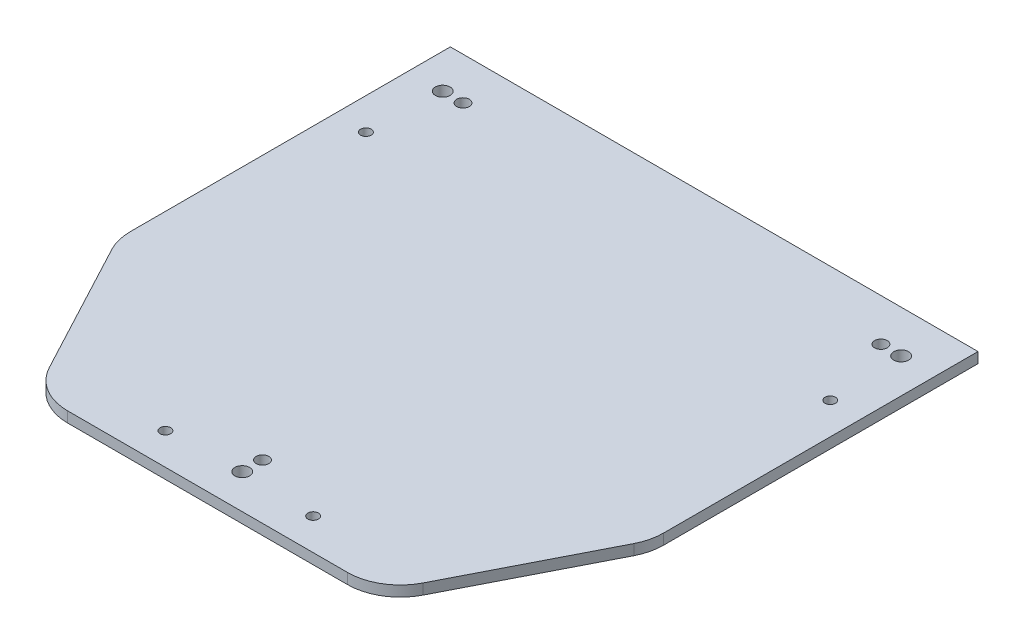
SolidWorks part; units mm, degrees
ref_plane "Plano frontal" through (0, 0, 0) normal (0, 0, 1) x (1, 0, 0)
ref_plane "Plano superior" through (0, 0, 0) normal (0, 1, 0) x (1, 0, 0)
ref_plane "Plano direito" through (0, 0, 0) normal (1, 0, 0) x (0, 0, -1)
sketch "Esboço1" plane through (0, 0, 0) normal (0, 1, 0) x (1, 0, 0)
  line L0 (602.5273, -115.797) -> (470.0074, -115.797)
  line L2 (411.2674, 124.203) -> (661.2674, 124.203)
  line L3 (661.2674, 84.203) -> (661.2674, -24.7556)
  line L4 (411.2674, 81.5882) -> (411.2674, -27.3704)
  line L5 (661.2674, 124.203) -> (661.2674, 84.203)
  line L12 (624.7901, -102.1709) -> (658.5302, -36.1295)
  line L14 (411.2674, 124.203) -> (411.2674, 81.5882)
  line L16 (447.936, -102.538) -> (414.1959, -39.1114)
  arc A0 (414.1959, -39.1114) -> (411.2674, -27.3704) centre (436.2674, -27.3704) cw
  arc A1 (447.936, -102.538) -> (470.0074, -115.797) centre (470.0074, -90.797) ccw
  arc A2 (624.7901, -102.1709) -> (602.5273, -115.797) centre (602.5273, -90.797) cw
  arc A3 (658.5302, -36.1295) -> (661.2674, -24.7556) centre (636.2674, -24.7556) ccw
  dimension "D3" = 240
  dimension "D1" = 25
  dimension "D2" = 250
extrude "Ressalto-extrusão4" add sketch "Esboço1" along normal blind 5 contours L14 region at (536.1641, 0, -10.3309)
sketch "Esboço2" plane through (0, 5, 0) normal (0, 1, 0) x (1, 0, 0)
  line L0 (411.2674, 124.203) -> (661.2674, 124.203) construction
  line L1 (536.2674, -115.797) -> (536.2674, -99.397) construction
  line L2 (426.2674, 69.0882) -> (426.2674, 69.203) construction
  line L3 (426.2674, 69.203) -> (411.2674, 69.203) construction
  line L4 (602.5273, -115.797) -> (470.0074, -115.797) construction
  line L5 (536.2674, -115.797) -> (536.2674, -89.797) construction
  line L6 (571.2674, -115.797) -> (571.2674, -100.797) construction
  line L7 (571.2674, -100.797) -> (568.7674, -100.797) construction
  line L8 (661.2674, 124.203) -> (661.2674, 104.203) construction
  line L9 (661.2674, 124.203) -> (661.2674, -24.7556) construction
  line L10 (503.7674, -100.797) -> (501.2674, -100.797) construction
  line L11 (501.2674, -100.797) -> (501.2674, -115.797) construction
  line L12 (661.2674, 104.203) -> (644.8674, 104.203) construction
  line L13 (661.2674, 69.203) -> (646.2674, 69.203) construction
  line L14 (661.2674, 104.203) -> (635.2674, 104.203) construction
  line L15 (411.2674, 124.203) -> (411.2674, 104.203) construction
  line L17 (411.2674, 124.203) -> (411.2674, -27.3704) construction
  line L18 (411.2674, 104.203) -> (427.6674, 104.203) construction
  line L19 (411.2674, 104.203) -> (437.2674, 104.203) construction
  circle A0 centre (571.2674, -100.797) radius 2.5
  circle A1 centre (501.2674, -100.797) radius 2.5
  circle A2 centre (646.2674, 69.203) radius 2.5
  circle A4 centre (426.2674, 69.203) radius 2.5
  circle A5 centre (536.2674, -99.397) radius 3.5
  circle A6 centre (536.2674, -89.797) radius 3
  circle A7 centre (644.8674, 104.203) radius 3.5
  circle A8 centre (635.2674, 104.203) radius 3
  circle A9 centre (427.6674, 104.203) radius 3.5
  circle A10 centre (437.2674, 104.203) radius 3
  dimension "D1" = 15
  dimension "D2" = 55
  dimension "D3" = 55
  dimension "D4" = 15
  dimension "D5" = 15
  dimension "D8" = 15
  dimension "D9" = 70
extrude "Corte-extrusão1" cut sketch "Esboço2" against normal blind 5
